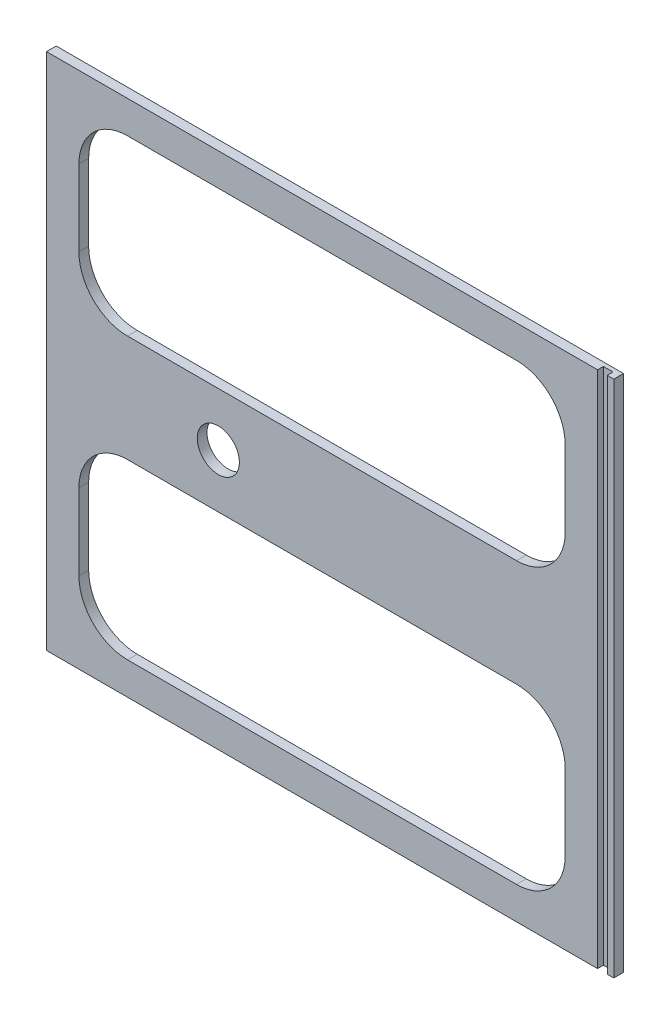
SolidWorks part; units mm, degrees
ref_plane "Front Plane" through (0, 0, 0) normal (0, 0, 1) x (1, 0, 0)
ref_plane "Top Plane" through (0, 0, 0) normal (0, 1, 0) x (1, 0, 0)
ref_plane "Right Plane" through (0, 0, 0) normal (1, 0, 0) x (0, 0, -1)
sketch "Sketch1" plane through (0, 0, 0) normal (0, 0, 1) x (1, 0, 0)
  line L1 (0, 0) -> (87.5, 0)
  line L2 (0, 0) -> (0, 80)
  line L3 (0, 80) -> (87.5, 80)
  line L4 (87.5, 0) -> (87.5, 80)
  dimension "D1" = 80
  dimension "D2" = 87.5
extrude "Boss-Extrude1" add sketch "Sketch1" along normal blind 1.5
sketch "Sketch2" plane through (0, 80, 0) normal (0, 1, 0) x (1, 0, 0)
  line L1 (87.5, -1.5) -> (0, -1.5) construction
  line L2 (86.5, -0.6) -> (85, -0.6)
  line L5 (85, -0.6) -> (85, -1.5)
  line L21 (85, -1.5) -> (86.5, -1.5)
  line L27 (86.5, -0.6) -> (87.5, -0.6) construction
  line L28 (87.5, -1.5) -> (87.5, 0) construction
  line L29 (86.5, -0.6) -> (86.5, -1.5)
  line M7 (0, -1.5) -> (87.5, -1.5)
  dimension "D1" = 1
  dimension "D2" = 1.5
  dimension "D3" = 0.9
extrude "Cut-Extrude1" cut sketch "Sketch2" against normal up to surface (80 mm away) contours L29 M7 region at (85.75, 80, 1.05) up to face at (43.75, 0, 0.75)
sketch "Sketch3" plane through (0, 0, 0) normal (0, 0, -1) x (-1, 0, 0)
  circle A1 centre (-26.5, 40) radius 3.25
  dimension "D1" = 6.5
extrude "Cut-Extrude2" cut sketch "Sketch3" against normal up to surface (1.5 mm away) up to face at (42.5, 40, 1.5)
sketch "Sketch4" plane through (0, 0, 1.5) normal (0, 0, 1) x (1, 0, 0)
  line L0 (5, 75) -> (0, 75) construction
  line L1 (12.5, 75) -> (72.5, 75)
  line L2 (5, 67.5) -> (5, 55.75)
  line L3 (12.5, 48.25) -> (72.5, 48.25)
  line L4 (80, 67.5) -> (80, 55.75)
  line L5 (0, 80) -> (0, 0) construction
  line L6 (0, 75) -> (5, 75)
  line L7 (5, 75) -> (5, 80) construction
  line L8 (85, 80) -> (0, 80) construction
  line L9 (80, 75) -> (85, 75)
  line L10 (85, 0) -> (85, 80) construction
  line L11 (26.5, 43.25) -> (26.5, 48.25) construction
  line L12 (23.25, 40) -> (0, 40) construction
  line L13 (12.5, 31.75) -> (72.5, 31.75)
  line L14 (80, 12.5) -> (80, 24.25)
  line L15 (12.5, 5) -> (72.5, 5)
  line L16 (5, 12.5) -> (5, 24.25)
  circle A0 centre (26.5, 40) radius 3.25 construction
  arc A1 (5, 55.75) -> (12.5, 48.25) centre (12.5, 55.75) ccw
  arc A2 (72.5, 48.25) -> (80, 55.75) centre (72.5, 55.75) ccw
  arc A3 (72.5, 75) -> (80, 67.5) centre (72.5, 67.5) cw
  arc A4 (12.5, 75) -> (5, 67.5) centre (12.5, 67.5) ccw
  arc A5 (12.5, 5) -> (5, 12.5) centre (12.5, 12.5) cw
  arc A6 (80, 12.5) -> (72.5, 5) centre (72.5, 12.5) cw
  arc A7 (72.5, 31.75) -> (80, 24.25) centre (72.5, 24.25) cw
  arc A8 (12.5, 31.75) -> (5, 24.25) centre (12.5, 24.25) ccw
  point P26 (5, 48.25)
  point P29 (80, 48.25)
  point P38 (5, 5)
  point P41 (80, 5)
  point P44 (80, 31.75)
  point P47 (5, 31.75)
  dimension "D5" = 7.5
  dimension "D6" = 7.5
  dimension "D1" = 5
  dimension "D2" = 5
  dimension "D3" = 5
  dimension "D4" = 5
extrude "Cut-Extrude3" cut sketch "Sketch4" against normal up to surface (1.5 mm away) contours L4 L1 L2 L3 | L16 L15 L14 L13 region at (42.5, 61.625, 1.5) region at (42.5, 18.375, 1.5) up to face at (23.25, 40, 0)
